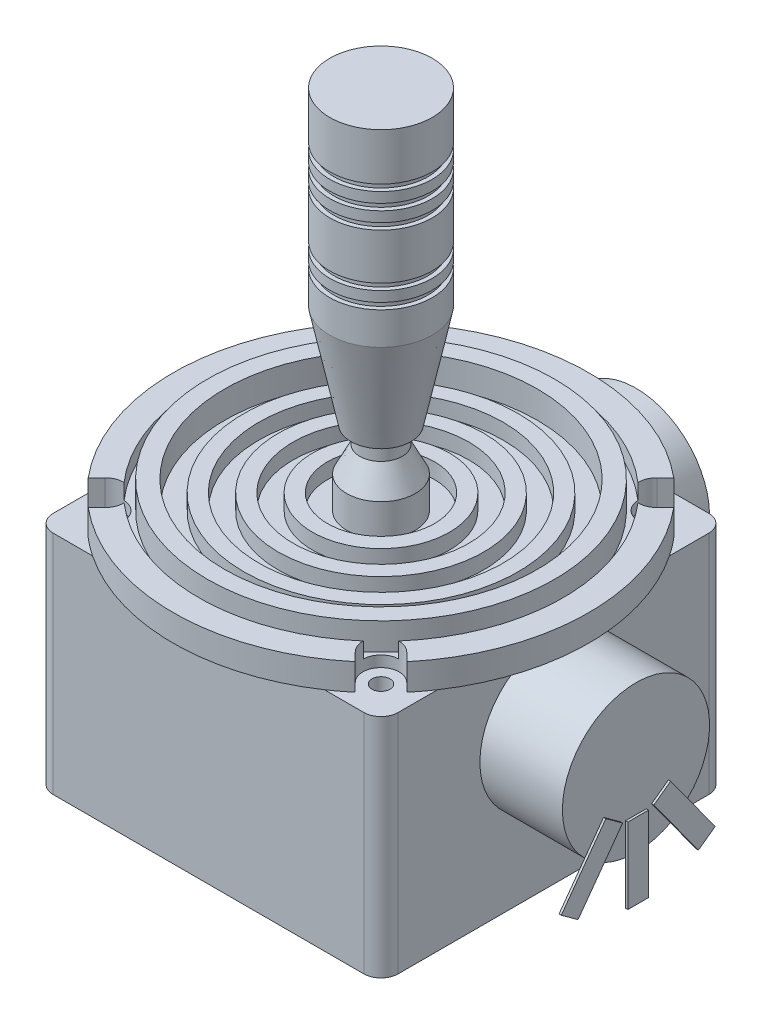
SolidWorks part; units mm, degrees
ref_plane "Front Plane" through (0, 0, 0) normal (0, 0, 1) x (1, 0, 0)
ref_plane "Top Plane" through (0, 0, 0) normal (0, 1, 0) x (1, 0, 0)
ref_plane "Right Plane" through (0, 0, 0) normal (1, 0, 0) x (0, 0, -1)
sketch "Sketch1" plane through (0, 0, 0) normal (0, 1, 0) x (1, 0, 0)
  line L1 (18.125, 20.125) -> (-18.125, 20.125)
  line L2 (20.125, 18.125) -> (20.125, -18.125)
  line L3 (18.125, -20.125) -> (-18.125, -20.125)
  line L4 (-20.125, 18.125) -> (-20.125, -18.125)
  line L5 (20.125, 20.125) -> (-20.125, -20.125) construction
  line L6 (20.125, -20.125) -> (-20.125, 20.125) construction
  arc A0 (-18.125, -20.125) -> (-20.125, -18.125) centre (-18.125, -18.125) cw
  arc A1 (18.125, 20.125) -> (20.125, 18.125) centre (18.125, 18.125) cw
  arc A2 (20.125, -18.125) -> (18.125, -20.125) centre (18.125, -18.125) cw
  arc A3 (-18.125, 20.125) -> (-20.125, 18.125) centre (-18.125, 18.125) ccw
  point P0 (0, 0)
  dimension "D2" = 2
  dimension "D1" = 40.25
extrude "Boss-Extrude1" add sketch "Sketch1" along normal mid plane 26.42
sketch "Sketch2" plane through (20.125, 0, 0) normal (1, 0, 0) x (0, 0, -1)
  line L0 (-18.125, 13.21) -> (18.125, 13.21) construction
  circle A0 centre (0, 3.395) radius 8.585
  point P6 (0, 12.1634)
  dimension "D2" = 17.17
  dimension "D1" = 1.23
extrude "Boss-Extrude2" add sketch "Sketch2" along normal blind 9.63
sketch "Sketch3" plane through (29.755, 0, 0) normal (1, 0, 0) x (0, 0, -1)
  line L0 (0, -10.22) -> (0, -5.19) construction
  line L1 (-1.21, -1.37) -> (1.21, -1.37)
  line L2 (-1.21, -1.37) -> (-1.21, -10.22)
  line L3 (-1.21, -10.22) -> (1.21, -10.22)
  line L4 (1.21, -1.37) -> (1.21, -10.22)
  circle A0 centre (0, 3.395) radius 8.585 construction
  dimension "D1" = 5.03
  dimension "D2" = 2.42
  dimension "D3" = 8.85
extrude "Boss-Extrude3" add sketch "Sketch3" along normal blind 0.26
pattern_circular "CirPattern2" count 10 every 36 about axis through (29.755, 3.395, 0) along (1, 0, 0) skipping 2, 3, 4, 5, 6, 7, 8 of "Boss-Extrude3"
ref_axis "Axis1" through (0, -14.531, 0) along (0, 1, 0)
pattern_circular "CirPattern1" count 2 every 90 about axis through (0, -14.531, 0) along (0, 1, 0) of "Boss-Extrude2", "Boss-Extrude3", "CirPattern2"
sketch "Sketch5" plane through (0, 0, 0) normal (0, 0, 1) x (1, 0, 0)
  line L0 (0, 0) -> (0, 114.42) construction
  line L1 (0, 13.21) -> (-24.25, 13.21)
  line L3 (-18.125, 13.21) -> (18.125, 13.21) construction
  line L4 (-24.25, 13.21) -> (-24.25, 16.3)
  line L5 (-24.25, 16.3) -> (-21.25, 16.3)
  line L6 (-21.25, 16.3) -> (-21.25, 14.49)
  line L7 (-21.25, 14.49) -> (-20.25, 14.49)
  line L8 (-20.25, 14.49) -> (-20.25, 17.66)
  line L9 (-20.25, 17.66) -> (-18.25, 17.66)
  line L10 (-18.25, 17.66) -> (-18.25, 14.49)
  line L11 (-18.25, 14.49) -> (-16, 14.49)
  line L12 (-16, 14.49) -> (-16, 16.3)
  line L13 (-16, 16.3) -> (-14.25, 16.3)
  line L14 (-14.25, 16.3) -> (-14.25, 14.49)
  line L15 (-14.25, 14.49) -> (-12, 14.49)
  line L16 (-12, 14.49) -> (-12, 16.3)
  line L17 (-12, 16.3) -> (-10.25, 16.3)
  line L18 (-10.25, 16.3) -> (-10.25, 14.49)
  line L19 (-10.25, 14.49) -> (-8, 14.49)
  line L20 (-8, 14.49) -> (-8, 16.3)
  line L21 (-8, 16.3) -> (-6.25, 16.3)
  line L22 (-6.25, 16.3) -> (-6.25, 14.49)
  line L23 (-6.25, 14.49) -> (-4, 14.49)
  line L24 (-4, 14.49) -> (-4, 18.21)
  line L25 (-4, 18.21) -> (-2.485, 21.21)
  line L26 (-2.485, 21.21) -> (-2.485, 23.21)
  line L27 (-2.485, 23.21) -> (-3.5, 23.21)
  line L28 (-3.5, 23.21) -> (-5.985, 35.21)
  line L29 (-5.985, 35.21) -> (-5.985, 39)
  line L30 (-5.985, 39) -> (-5.485, 39)
  line L31 (-5.485, 39) -> (-5.485, 39.75)
  line L32 (-5.485, 39.75) -> (-5.985, 39.75)
  line L33 (-5.985, 39.75) -> (-5.985, 40.95)
  line L34 (-5.985, 40.95) -> (-5.485, 40.95)
  line L35 (-5.485, 40.95) -> (-5.485, 41.7)
  line L36 (-5.485, 41.7) -> (-5.985, 41.7)
  line L37 (-5.985, 41.7) -> (-5.985, 47.06)
  line L38 (-5.985, 47.06) -> (-5.485, 47.06)
  line L39 (-5.485, 47.06) -> (-5.485, 47.81)
  line L40 (-5.485, 47.81) -> (-5.985, 47.81)
  line L41 (-5.985, 47.81) -> (-5.985, 49.01)
  line L42 (-5.985, 49.01) -> (-5.485, 49.01)
  line L43 (-5.485, 49.01) -> (-5.485, 49.76)
  line L44 (-5.485, 49.76) -> (-5.985, 49.76)
  line L45 (-5.985, 49.76) -> (-5.985, 50.96)
  line L46 (-5.985, 50.96) -> (-5.485, 50.96)
  line L47 (-5.485, 50.96) -> (-5.485, 51.71)
  line L48 (-5.485, 51.71) -> (-5.985, 51.71)
  line L49 (-5.985, 51.71) -> (-5.985, 57.21)
  line L50 (-5.985, 57.21) -> (0, 57.21)
  line L51 (0, 57.21) -> (0, 13.21)
  point P54 (-16.3551, 16.3)
  point P55 (-25.57, 16.3)
  point P56 (-13.3214, 16.3)
  dimension "D1" = 4.97
  dimension "D2" = 11.97
  dimension "D3" = 44
  dimension "D4" = 5.5
  dimension "D5" = 1.2
  dimension "D6" = 0.75
  dimension "D7" = 0.5
  dimension "D8" = 5.36
  dimension "D9" = 22
  dimension "D10" = 7
  dimension "D11" = 34
  dimension "D12" = 2
  dimension "D13" = 8
  dimension "D14" = 5
  dimension "D15" = 3.09
  dimension "D16" = 4.45
  dimension "D17" = 2.25
  dimension "D18" = 3.17
  dimension "D19" = 1.75
  dimension "D20" = 2
  dimension "D21" = 3
  dimension "D22" = 48.5
revolve "Revolve1" add sketch "Sketch5" angle 360 about L0
sketch "Sketch6" plane through (0, 16.3, 0) normal (0, 1, 0) x (1, 0, 0)
  line L0 (-17.5928, 14.5876) -> (-18.584, 15.5788)
  line L1 (-14.5876, 17.5928) -> (-15.5788, 18.584)
  line L2 (-17.1473, 17.1473) -> (-14.5876, 14.5876) construction
  line L3 (0, 0) -> (-19.5392, 19.5392) construction
  line L4 (14.5876, 17.5928) -> (15.5788, 18.584)
  line L5 (17.5928, 14.5876) -> (18.584, 15.5788)
  line L6 (17.1473, 17.1473) -> (14.5876, 14.5876) construction
  line L7 (17.5928, -14.5876) -> (18.584, -15.5788)
  line L8 (14.5876, -17.5928) -> (15.5788, -18.584)
  line L9 (17.1473, -17.1473) -> (14.5876, -14.5876) construction
  line L10 (-14.5876, -17.5928) -> (-15.5788, -18.584)
  line L11 (-17.5928, -14.5876) -> (-18.584, -15.5788)
  line L12 (-17.1473, -17.1473) -> (-14.5876, -14.5876) construction
  arc A0 (-17.5928, 14.5876) -> (-14.5876, 17.5928) centre (-16.0902, 16.0902) ccw
  circle A1 centre (0, 0) radius 24.25 construction
  arc A2 (-15.5788, 18.584) -> (-18.584, 15.5788) centre (0, 0) ccw
  arc A3 (-18.125, 20.125) -> (-20.125, 18.125) centre (-18.125, 18.125) ccw construction
  arc A4 (14.5876, 17.5928) -> (17.5928, 14.5876) centre (16.0902, 16.0902) ccw
  arc A5 (18.584, 15.5788) -> (15.5788, 18.584) centre (0, 0) ccw
  arc A6 (17.5928, -14.5876) -> (14.5876, -17.5928) centre (16.0902, -16.0902) ccw
  arc A7 (15.5788, -18.584) -> (18.584, -15.5788) centre (0, 0) ccw
  arc A8 (-14.5876, -17.5928) -> (-17.5928, -14.5876) centre (-16.0902, -16.0902) ccw
  arc A9 (-18.584, -15.5788) -> (-15.5788, -18.584) centre (0, 0) ccw
  point P37 (0, 0)
  dimension "D1" = 4.25
  dimension "D2" = 3.62
  dimension "D3" = 4
extrude "Cut-Extrude1" cut sketch "Sketch6" against normal up to surface (3.09 mm away) up to face at (-18.1597, 13.21, 18.1597)
sketch "Sketch7" plane through (0, 13.21, 0) normal (0, 1, 0) x (1, 0, 0)
  line L0 (0, 0) -> (-19.5392, 19.5392) construction
  line L1 (0, 0) -> (19.5392, 19.5392) construction
  line L2 (0, 0) -> (-29.8758, 0) construction
  circle A0 centre (-16.25, 16.25) radius 1.05
  arc A1 (-18.125, 20.125) -> (-20.125, 18.125) centre (-18.125, 18.125) ccw construction
  arc A2 (20.125, 18.125) -> (18.125, 20.125) centre (18.125, 18.125) ccw construction
  circle A3 centre (16.25, 16.25) radius 1.05
  circle A4 centre (16.25, -16.25) radius 1.05
  circle A5 centre (-16.25, -16.25) radius 1.05
  dimension "D1" = 2.1
  dimension "D2" = 32.5
extrude "Cut-Extrude2" cut sketch "Sketch7" against normal blind 4
